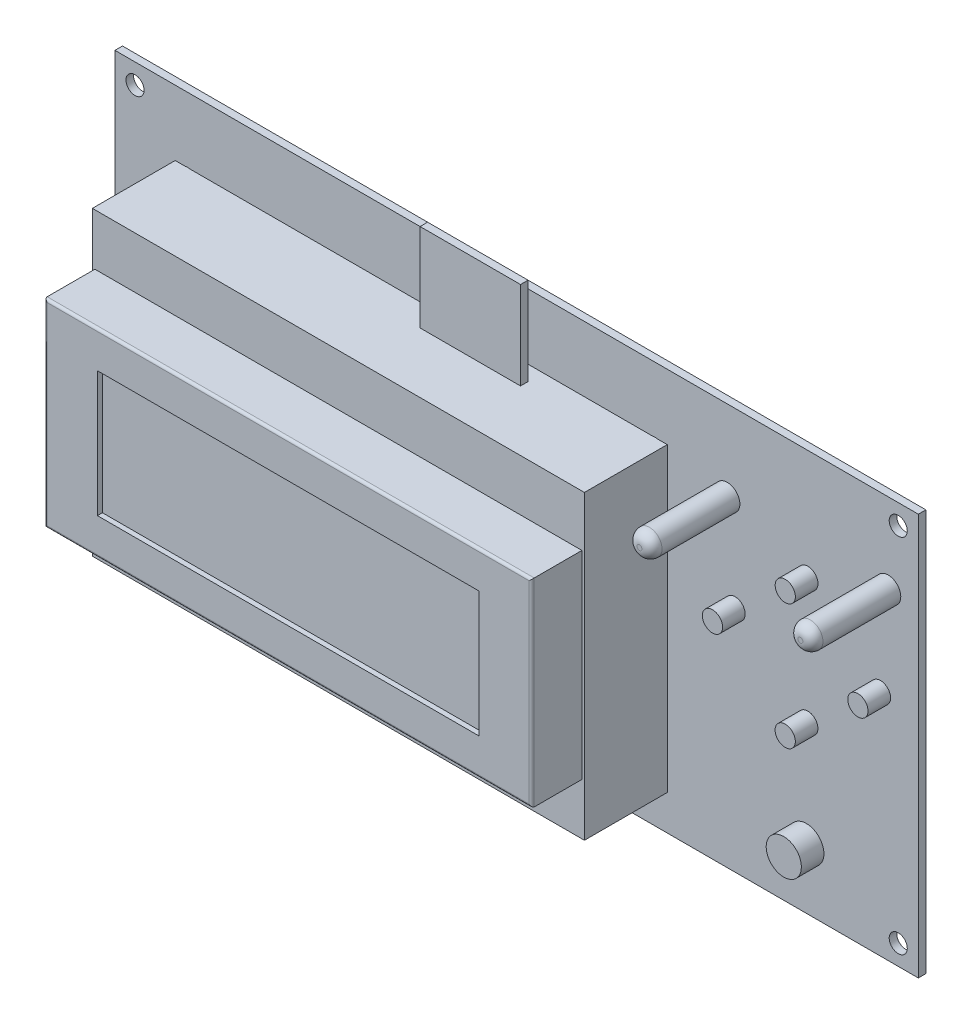
SolidWorks part; units mm, degrees
ref_plane "Płaszczyzna przednia" through (0, 0, 0) normal (0, 0, 1) x (1, 0, 0)
ref_plane "Płaszczyzna górna" through (0, 0, 0) normal (0, 1, 0) x (1, 0, 0)
ref_plane "Płaszczyzna prawa" through (0, 0, 0) normal (1, 0, 0) x (0, 0, -1)
sketch "Model" plane through (0, 0, 0) normal (0, 0, 1) x (1, 0, 0)
  line L7 (70.19, 57.27) -> (79.715, 57.27)
  line L8 (70.19, 54.73) -> (70.19, 57.27)
  line L9 (79.715, 57.27) -> (80.35, 56.635)
  line L10 (80.35, 56.635) -> (80.35, 54.73)
  line L11 (80.35, 54.73) -> (70.19, 54.73)
  line L40 (12, 67) -> (110, 67)
  line L41 (12, 7) -> (12, 67)
  line L42 (12.5, 56.75) -> (12.5, 17.25)
  line L43 (12.5, 17.25) -> (109.5, 17.25)
  line L44 (23, 49.5) -> (99, 49.5)
  line L45 (23, 24.5) -> (23, 49.5)
  line L46 (25.8, 47.4) -> (25.8, 26.6)
  line L47 (25.8, 26.6) -> (96.2, 26.6)
  line L48 (96.2, 47.4) -> (25.8, 47.4)
  line L49 (96.2, 26.6) -> (96.2, 47.4)
  line L50 (99, 49.5) -> (99, 24.5)
  line L51 (99, 24.5) -> (23, 24.5)
  line L52 (109.5, 56.75) -> (12.5, 56.75)
  line L53 (109.5, 17.25) -> (109.5, 56.75)
  line L54 (110, 67) -> (110, 7)
  line L55 (110, 7) -> (12, 7)
  line L194 (0, 80) -> (0, 0)
  line L195 (160, 0) -> (160, 80)
  line L196 (160, 80) -> (0, 80)
  line L197 (0, 0) -> (160, 0)
  circle A0 centre (152.4656, 45.5269) radius 2.0156
  circle A1 centre (138, 58) radius 2.0156
  circle A2 centre (137.7008, 12) radius 3.5
  circle A3 centre (154.0037, 64.0129) radius 2.5
  circle A4 centre (137.9897, 33.0224) radius 2.0156
  circle A8 centre (121.9578, 63.9642) radius 2.5
  circle A9 centre (123.4994, 45.5111) radius 2.0156
  circle A30 centre (4, 76) radius 1.8
  circle A41 centre (156, 76) radius 1.8
  circle A43 centre (156, 4) radius 1.8
  circle A60 centre (14.5, 64.5) radius 2.55
  circle A61 centre (107.5, 64.5) radius 2.55
  circle A62 centre (14.5, 9.5) radius 2.55
  circle A63 centre (107.5, 9.5) radius 2.55
  circle A65 centre (4, 4) radius 1.8
  dimension "D1" = 160
  dimension "D2" = 80
extrude "Dodanie-wyciągnięcie1" add sketch "Model" along normal blind 1.5 contours A63 L54 A61 L40 A60 L41 A62 L55 L53 L43 L42 L52 L8 L7 L9 | L194 L197 L195 L196 A65 A63 L55 A62 L41 A60 L40 A61 L54 A43 A41 A30 A9 A8 A4 A3 A2 A1 A0 | A60 L40 L41 | A61 L54 L40 | A63 L55 L54 | A62 L41 L55 region at (12.5189, 66.4811, 0) region at (61, 65.8509, 0) region at (109.4811, 66.4811, 0) region at (12.5189, 7.5189, 0) region at (109.4811, 7.5189, 0) region at (80, 78.2111, 0)
extrude "Dodanie-wyciągnięcie2" add sketch "Model<3>" along normal blind 6 contours A1 | A9 | A0 | A2 | A4 region at (152.4656, 45.5269, 0) region at (138, 58, 0) region at (137.7008, 12, 0) region at (137.9897, 33.0224, 0) region at (123.4994, 45.5111, 0)
sketch "Model<3>" plane through (0, 0, 0) normal (0, 0, 1) x (1, 0, 0) same geometry as "Model"
extrude "Dodanie-wyciągnięcie3" add sketch "Model<4>" along normal blind 19 contours A8 | A3 region at (154.0037, 64.0129, 0) region at (121.9578, 63.9642, 0)
sketch "Model<4>" plane through (0, 0, 0) normal (0, 0, 1) x (1, 0, 0) same geometry as "Model"
fillet "Zaokrąglenie1" radius 2 2 edges at (156.5037, 64.0129, 19) (124.4578, 63.9642, 19)
extrude "Dodanie-wyciągnięcie4" add sketch "Model<5>" along normal blind 18 contours L40 L54 L55 L41
sketch "Model<5>" plane through (0, 0, 0) normal (0, 0, 1) x (1, 0, 0) same geometry as "Model"
extrude "Dodanie-wyciągnięcie5" add sketch "Model<6>" along normal blind 28 contours L43 L53 L52 L42
sketch "Model<6>" plane through (0, 0, 0) normal (0, 0, 1) x (1, 0, 0) same geometry as "Model"
sketch "Szkic2" plane through (0, 0, 28) normal (0, 0, 1) x (1, 0, 0)
  line L4 (12.5, 56.75) -> (12.5, 17.25)
  line L5 (12.5, 17.25) -> (109.5, 17.25)
  line L6 (109.5, 17.25) -> (109.5, 56.75)
  line L7 (109.5, 56.75) -> (12.5, 56.75)
  line L8 (12.5, 56.75) -> (12.5, 17.25)
  line L9 (12.5, 17.25) -> (109.5, 17.25)
  line L10 (109.5, 17.25) -> (109.5, 56.75)
  line L11 (109.5, 56.75) -> (12.5, 56.75)
  line L12 (110, 7) -> (110, 67)
  line L13 (110, 67) -> (12, 67)
  line L14 (12, 67) -> (12, 7)
  line L15 (12, 7) -> (110, 7)
  line L16 (110, 7) -> (110, 67)
  line L17 (110, 67) -> (12, 67)
  line L18 (12, 67) -> (12, 7)
  line L19 (12, 7) -> (110, 7)
  line L20 (109.5, 17.25) -> (109.5, 56.75)
  line L21 (12.5, 17.25) -> (109.5, 17.25)
  line L22 (12.5, 56.75) -> (12.5, 17.25)
  line L23 (109.5, 56.75) -> (12.5, 56.75)
  line L24 (109.5, 17.25) -> (109.5, 56.75)
  line L25 (12.5, 17.25) -> (109.5, 17.25)
  line L26 (12.5, 56.75) -> (12.5, 17.25)
  line L27 (109.5, 56.75) -> (12.5, 56.75)
  line L28 (25.8, 47.4) -> (25.8, 26.6)
  line L29 (25.8, 26.6) -> (96.2, 26.6)
  line L30 (96.2, 26.6) -> (96.2, 47.4)
  line L31 (96.2, 47.4) -> (25.8, 47.4)
  line L32 (25.8, 47.4) -> (25.8, 26.6)
  line L33 (25.8, 26.6) -> (96.2, 26.6)
  line L34 (96.2, 26.6) -> (96.2, 47.4)
  line L35 (96.2, 47.4) -> (25.8, 47.4)
  line L36 (23, 49.5) -> (23, 24.5)
  line L37 (99, 49.5) -> (23, 49.5)
  line L38 (99, 24.5) -> (99, 49.5)
  line L39 (23, 24.5) -> (99, 24.5)
  line L40 (23, 49.5) -> (23, 24.5)
  line L41 (99, 49.5) -> (23, 49.5)
  line L42 (99, 24.5) -> (99, 49.5)
  line L43 (23, 24.5) -> (99, 24.5)
  line L44 (0, 80) -> (0, 0)
  line L45 (0, 0) -> (160, 0)
  line L46 (160, 0) -> (160, 80)
  line L47 (160, 80) -> (0, 80)
  line L48 (0, 80) -> (0, 0)
  line L49 (0, 0) -> (160, 0)
  line L50 (160, 0) -> (160, 80)
  line L51 (160, 80) -> (0, 80)
  line L53 (79.715, 57.27) -> (70.19, 57.27)
  line L54 (80.35, 56.635) -> (79.715, 57.27)
  line L55 (80.35, 54.73) -> (80.35, 56.635)
  line L56 (70.19, 54.73) -> (80.35, 54.73)
  line L57 (70.19, 57.27) -> (70.19, 54.73)
  line L58 (79.715, 57.27) -> (70.19, 57.27)
  line L59 (80.35, 56.635) -> (79.715, 57.27)
  line L60 (80.35, 54.73) -> (80.35, 56.635)
  line L61 (70.19, 54.73) -> (80.35, 54.73)
  line L62 (70.19, 57.27) -> (70.19, 54.73)
  circle A1 centre (137.9897, 33.0224) radius 2.0156
  circle A2 centre (137.9897, 33.0224) radius 2.0156
  circle A3 centre (154.0037, 64.0129) radius 2.5
  circle A4 centre (154.0037, 64.0129) radius 2.5
  circle A5 centre (137.7008, 12) radius 3.5
  circle A6 centre (137.7008, 12) radius 3.5
  circle A7 centre (138, 58) radius 2.0156
  circle A8 centre (138, 58) radius 2.0156
  circle A9 centre (152.4656, 45.5269) radius 2.0156
  circle A10 centre (152.4656, 45.5269) radius 2.0156
  circle A11 centre (123.4994, 45.5111) radius 2.0156
  circle A12 centre (123.4994, 45.5111) radius 2.0156
  circle A13 centre (121.9578, 63.9642) radius 2.5
  circle A14 centre (121.9578, 63.9642) radius 2.5
  circle A15 centre (4, 76) radius 1.8
  circle A16 centre (4, 76) radius 1.8
  circle A17 centre (156, 4) radius 1.8
  circle A18 centre (156, 4) radius 1.8
  circle A19 centre (156, 76) radius 1.8
  circle A20 centre (156, 76) radius 1.8
  circle A21 centre (107.5, 9.5) radius 2.55
  circle A22 centre (107.5, 9.5) radius 2.55
  circle A23 centre (14.5, 9.5) radius 2.55
  circle A24 centre (14.5, 9.5) radius 2.55
  circle A25 centre (107.5, 64.5) radius 2.55
  circle A26 centre (107.5, 64.5) radius 2.55
  circle A27 centre (14.5, 64.5) radius 2.55
  circle A28 centre (14.5, 64.5) radius 2.55
  circle A29 centre (4, 4) radius 1.8
  circle A30 centre (4, 4) radius 1.8
  dimension "D1" = 0
  dimension "D2" = 0
  dimension "D3" = 0
  dimension "D4" = 0
  dimension "D5" = 0
  dimension "D6" = 0
  dimension "D7" = 0
  dimension "D8" = 0
  dimension "D9" = 0
  dimension "D10" = 0
  dimension "D11" = 0
  dimension "D12" = 0
  dimension "D13" = 0
  dimension "D14" = 0
  dimension "D15" = 0
  dimension "D16" = 0
  dimension "D17" = 0
  dimension "D18" = 0
  dimension "D19" = 0
  dimension "D20" = 0
  dimension "D21" = 0
  dimension "D22" = 0
extrude "Wytnij-wyciągnięcie1" cut sketch "Szkic2" against normal blind 1 contours L40 L43 L42 L41
fillet "Zaokrąglenie2" radius 0.5 4 edges at (109.5, 37, 28) (61, 56.75, 28) (12.5, 37, 28) (61, 17.25, 28)
sketch "Szkic3" plane through (0, 0, 1.5) normal (0, 0, 1) x (1, 0, 0)
  line L1 (65.27, 84.5) -> (85.27, 84.5)
  line L2 (65.27, 84.5) -> (65.27, 51)
  line L3 (65.27, 51) -> (85.27, 51)
  line L4 (110, 7) -> (110, 67)
  line L5 (110, 67) -> (12, 67)
  line L6 (12, 67) -> (12, 7)
  line L7 (12, 7) -> (110, 7)
  line L8 (110, 7) -> (110, 67)
  line L9 (110, 67) -> (12, 67)
  line L10 (12, 67) -> (12, 7)
  line L11 (12, 7) -> (110, 7)
  line L12 (109.5, 17.25) -> (109.5, 56.75)
  line L13 (12.5, 17.25) -> (109.5, 17.25)
  line L14 (12.5, 56.75) -> (12.5, 17.25)
  line L15 (109.5, 56.75) -> (12.5, 56.75)
  line L16 (109.5, 17.25) -> (109.5, 56.75)
  line L17 (12.5, 17.25) -> (109.5, 17.25)
  line L18 (12.5, 56.75) -> (12.5, 17.25)
  line L19 (109.5, 56.75) -> (12.5, 56.75)
  line L20 (25.8, 47.4) -> (25.8, 26.6)
  line L21 (25.8, 26.6) -> (96.2, 26.6)
  line L22 (96.2, 26.6) -> (96.2, 47.4)
  line L23 (96.2, 47.4) -> (25.8, 47.4)
  line L24 (25.8, 47.4) -> (25.8, 26.6)
  line L25 (25.8, 26.6) -> (96.2, 26.6)
  line L26 (96.2, 26.6) -> (96.2, 47.4)
  line L27 (96.2, 47.4) -> (25.8, 47.4)
  line L28 (23, 49.5) -> (23, 24.5)
  line L29 (99, 49.5) -> (23, 49.5)
  line L30 (99, 24.5) -> (99, 49.5)
  line L31 (23, 24.5) -> (99, 24.5)
  line L32 (23, 49.5) -> (23, 24.5)
  line L33 (99, 49.5) -> (23, 49.5)
  line L34 (99, 24.5) -> (99, 49.5)
  line L35 (23, 24.5) -> (99, 24.5)
  line L36 (0, 80) -> (0, 0)
  line L37 (0, 0) -> (160, 0)
  line L38 (160, 0) -> (160, 80)
  line L39 (160, 80) -> (0, 80)
  line L40 (0, 80) -> (0, 0)
  line L41 (0, 0) -> (160, 0)
  line L42 (160, 0) -> (160, 80)
  line L43 (160, 80) -> (0, 80)
  line L44 (85.27, 84.5) -> (85.27, 51)
  line L45 (79.715, 57.27) -> (70.19, 57.27)
  line L46 (80.35, 56.635) -> (79.715, 57.27)
  line L47 (80.35, 54.73) -> (80.35, 56.635)
  line L48 (70.19, 54.73) -> (80.35, 54.73)
  line L49 (70.19, 57.27) -> (70.19, 54.73)
  line L50 (79.715, 57.27) -> (70.19, 57.27)
  line L51 (80.35, 56.635) -> (79.715, 57.27)
  line L52 (80.35, 54.73) -> (80.35, 56.635)
  line L53 (70.19, 54.73) -> (80.35, 54.73)
  line L54 (70.19, 57.27) -> (70.19, 54.73)
  circle A1 centre (137.9897, 33.0224) radius 2.0156
  circle A2 centre (137.9897, 33.0224) radius 2.0156
  circle A3 centre (154.0037, 64.0129) radius 2.5
  circle A4 centre (154.0037, 64.0129) radius 2.5
  circle A5 centre (137.7008, 12) radius 3.5
  circle A6 centre (137.7008, 12) radius 3.5
  circle A7 centre (138, 58) radius 2.0156
  circle A8 centre (138, 58) radius 2.0156
  circle A9 centre (152.4656, 45.5269) radius 2.0156
  circle A10 centre (152.4656, 45.5269) radius 2.0156
  circle A11 centre (123.4994, 45.5111) radius 2.0156
  circle A12 centre (123.4994, 45.5111) radius 2.0156
  circle A13 centre (121.9578, 63.9642) radius 2.5
  circle A14 centre (121.9578, 63.9642) radius 2.5
  circle A15 centre (4, 76) radius 1.8
  circle A16 centre (4, 76) radius 1.8
  circle A17 centre (156, 4) radius 1.8
  circle A18 centre (156, 4) radius 1.8
  circle A19 centre (156, 76) radius 1.8
  circle A20 centre (156, 76) radius 1.8
  circle A21 centre (107.5, 9.5) radius 2.55
  circle A22 centre (107.5, 9.5) radius 2.55
  circle A23 centre (14.5, 9.5) radius 2.55
  circle A24 centre (14.5, 9.5) radius 2.55
  circle A25 centre (107.5, 64.5) radius 2.55
  circle A26 centre (107.5, 64.5) radius 2.55
  circle A27 centre (14.5, 64.5) radius 2.55
  circle A28 centre (14.5, 64.5) radius 2.55
  circle A29 centre (4, 4) radius 1.8
  circle A30 centre (4, 4) radius 1.8
  point P74 (75.27, 84.5)
  point P75 (75.27, 54.73)
  dimension "D22" = 20
  dimension "D23" = 33.5
  dimension "D24" = 4.5
  dimension "D1" = 0
  dimension "D2" = 0
  dimension "D3" = 0
  dimension "D4" = 0
  dimension "D5" = 0
  dimension "D6" = 0
  dimension "D7" = 0
  dimension "D8" = 0
  dimension "D9" = 0
  dimension "D10" = 0
  dimension "D11" = 0
  dimension "D12" = 0
  dimension "D13" = 0
  dimension "D14" = 0
  dimension "D15" = 0
  dimension "D16" = 0
  dimension "D17" = 0
  dimension "D18" = 0
  dimension "D19" = 0
  dimension "D20" = 0
  dimension "D21" = 0
extrude "Dodanie-wyciągnięcie6" add sketch "Szkic3" along normal blind 1.5 from offset 3 contours L1 L44 L3 L2
